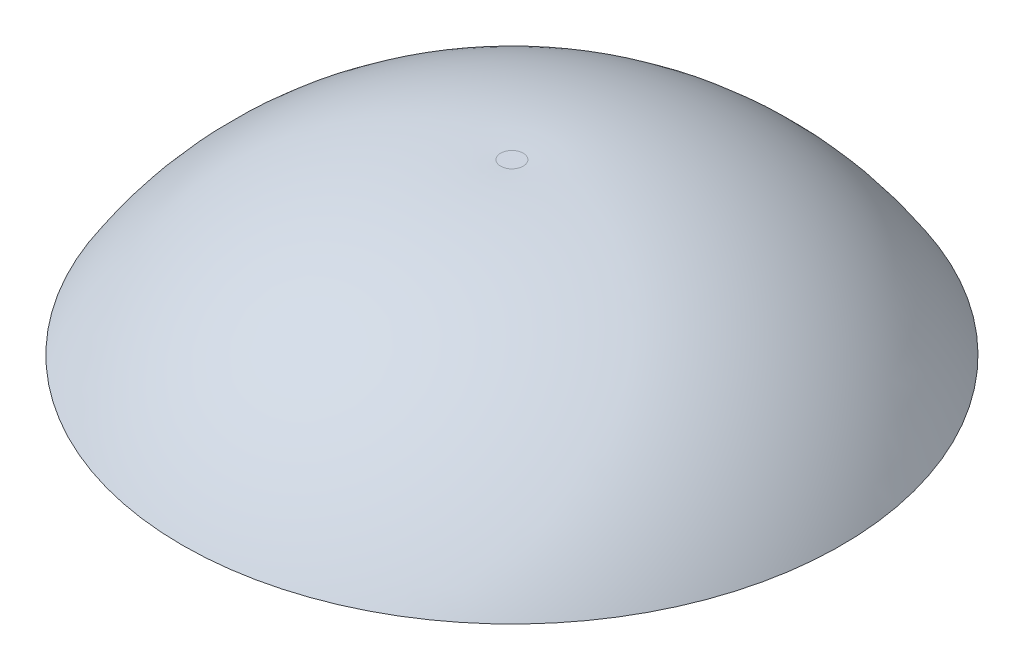
SolidWorks part; units mm, degrees
ref_plane "Front Plane" through (0, 0, 0) normal (0, 0, 1) x (1, 0, 0)
ref_plane "Top Plane" through (0, 0, 0) normal (0, 1, 0) x (1, 0, 0)
ref_plane "Right Plane" through (0, 0, 0) normal (1, 0, 0) x (0, 0, -1)
sketch "Sketch1" plane through (0, 0, 0) normal (0, 0, 1) x (1, 0, 0)
  line L1 (9.525, 104.902) -> (9.525, 95.25)
  line L4 (3.937, 95.25) -> (9.525, 95.25)
  line L5 (3.937, 97.79) -> (6.35, 97.79)
  line L6 (-9.525, 104.902) -> (-9.525, 95.25)
  line L9 (-3.937, 95.25) -> (-9.525, 95.25)
  line L16 (-3.937, 97.79) -> (-6.35, 97.79)
  line L17 (-9.525, 104.902) -> (9.525, 104.902)
  line L18 (-6.35, 97.79) -> (-6.35, 101.6)
  line L19 (0, 133.35) -> (0, 94.2799)
  line L20 (6.35, 101.6) -> (9.525, 101.6)
  line L21 (-6.35, 101.6) -> (6.35, 101.6)
  line L22 (6.35, 101.6) -> (6.35, 97.79)
  line L24 (74.2444, 95.25) -> (72.0871, 93.9092)
  line L25 (5.08, 130.8663) -> (2.54, 130.8663)
  line L28 (9.525, 101.6) -> (-6.35, 101.6)
  line L31 (-6.35, 101.6) -> (-9.525, 101.6)
  line L32 (-5.08, 130.8663) -> (-2.54, 130.8663)
  line L33 (-74.2444, 95.25) -> (-72.0871, 93.9092)
  line L34 (-2.54, 133.35) -> (2.54, 133.35)
  line L35 (-2.54, 133.35) -> (-2.54, 104.902)
  line L36 (2.54, 130.8663) -> (-2.54, 130.8663)
  line L37 (2.54, 133.35) -> (2.54, 104.902)
  line L38 (-62.7536, 89.0848) -> (-64.9533, 90.3548)
  line L40 (-7.6199, 133.3828) -> (-7.6199, 130.842)
  line L41 (7.6199, 133.3828) -> (7.6199, 130.842)
  line L48 (2.54, 133.35) -> (2.54, 94.2799) construction
  line L49 (-2.54, 133.35) -> (-2.54, 94.2799) construction
  line L51 (-3.937, 97.79) -> (-3.937, 95.25)
  line L52 (3.937, 97.79) -> (3.937, 95.25)
  line L53 (3.937, 97.536) -> (3.937, 95.504)
  line L55 (3.683, 97.79) -> (6.35, 97.79) construction
  line L56 (3.683, 95.25) -> (9.525, 95.25) construction
  line L61 (-3.683, 95.25) -> (-9.525, 95.25) construction
  line L62 (-3.683, 97.79) -> (-6.35, 97.79) construction
  line L63 (-3.937, 97.536) -> (-3.937, 95.504)
  line L107 (-6.604, 97.536) -> (-6.604, 101.6) construction
  line L108 (-3.937, 97.536) -> (-6.604, 97.536) construction
  line L109 (-3.937, 95.504) -> (-9.271, 95.504) construction
  line L110 (-9.271, 104.648) -> (-9.271, 95.504) construction
  line L111 (-9.271, 104.648) -> (9.271, 104.648) construction
  line L112 (6.604, 101.6) -> (6.604, 97.536) construction
  line L113 (3.937, 97.536) -> (6.604, 97.536) construction
  line L114 (3.937, 95.504) -> (9.271, 95.504) construction
  line L115 (9.271, 104.648) -> (9.271, 95.504) construction
  line L116 (-3.683, 97.79) -> (-3.683, 95.25) construction
  line L117 (3.683, 97.79) -> (3.683, 95.25) construction
  arc A0 (2.54, 133.35) -> (74.2444, 95.25) centre (5.6018, 52.5883) cw
  arc A1 (5.08, 130.8663) -> (72.0871, 93.9092) centre (5.6018, 52.5883) cw
  arc A2 (-5.08, 130.8663) -> (-72.0871, 93.9092) centre (-5.6018, 52.5883) ccw
  arc A3 (-2.54, 133.35) -> (-74.2444, 95.25) centre (-5.6018, 52.5883) ccw
  point P11 (3.81, 25.4)
  point P14 (10.7436, 6.35)
  point P18 (-0.6484, 19.0832)
  point P19 (6.2973, 0)
  point P24 (12.7, 0)
  point P26 (12.7, 25.4)
  point P28 (0, 38.1)
  point P31 (12.1451, 41.8131)
  point P32 (0, 38.1)
  point P33 (19.05, 38.1)
  point P57 (0, 101.6)
  point P72 (-1.27, 101.6)
  point P73 (-1.27, -11.7576)
  point P74 (1.27, 101.6)
  point P75 (1.27, -11.7576)
  point P84 (0, 104.902)
  point P94 (-3.81, 104.902)
  point P101 (64.9533, 90.3548)
  point P104 (62.2037, 88.7673)
  dimension "D3" = 2.54
  dimension "D7" = 12.7
revolve "Revolve4" add sketch "Sketch1" angle 360 about L19 region at (4.7625, 103.251, 0)
revolve "Revolve5" add sketch "Sketch1<21>" angle 90 mid plane about L19 region at (7.2861, 97.9809, 0) region at (-7.2861, 97.9809, 0)
sketch "Sketch1<21>" plane through (0, 0, 0) normal (0, 0, 1) x (1, 0, 0) same geometry as "Sketch1"
revolve "Revolve7" add sketch "Sketch1<24>" angle 360 about L19 region at (1.27, 117.8841, 0) region at (1.27, 132.1081, 0)
sketch "Sketch1<24>" plane through (0, 0, 0) normal (0, 0, 1) x (1, 0, 0) same geometry as "Sketch1"
revolve "Revolve8" add sketch "Sketch1<32>" angle 360 about L19 region at (5.0878, 132.1284, 0) region at (1.27, 132.1081, 0)
sketch "Sketch1<32>" plane through (0, 0, 0) normal (0, 0, 1) x (1, 0, 0) same geometry as "Sketch1"
revolve "Revolve9" add sketch "Sketch1<36>" angle 360 about L19 region at (8.3943, 132.1124, 0)
sketch "Sketch1<36>" plane through (0, 0, 0) normal (0, 0, 1) x (1, 0, 0) same geometry as "Sketch1"
